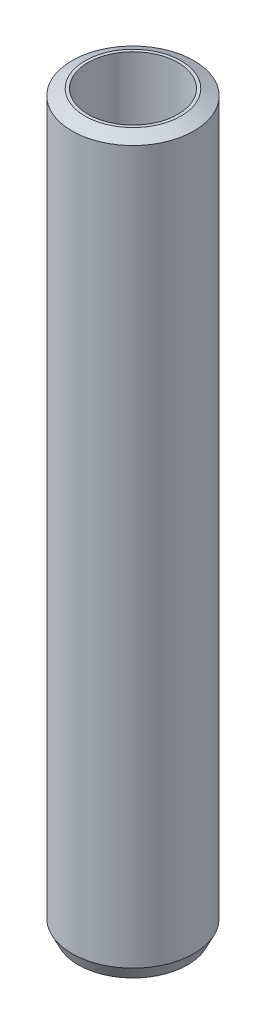
SolidWorks part; units mm, degrees
ref_plane "Front Plane" through (0, 0, 0) normal (0, 0, 1) x (1, 0, 0)
ref_plane "Top Plane" through (0, 0, 0) normal (0, 1, 0) x (1, 0, 0)
ref_plane "Right Plane" through (0, 0, 0) normal (1, 0, 0) x (0, 0, -1)
sketch "Sketch1" plane through (0, 0, 0) normal (0, 1, 0) x (1, 0, 0)
  circle A0 centre (0, 0) radius 50
  dimension "SHAFT_OD" = 100
extrude "Boss-Extrude1" add sketch "Sketch1" along normal blind 600
sketch "Sketch2" plane through (0, 0, 0) normal (0, 1, 0) x (1, 0, 0)
  circle A0 centre (0, 0) radius 36.8509
  dimension "BORE_D" = 73.7018
extrude "Cut-Extrude1" cut sketch "Sketch2" along normal through all
chamfer "Chamfer1" distance 5.2314 angle 63.895 2 edges at (0, 600, 50) (0, 0, 50) first distance on face at (0, 600, 50) first distance on face at (0, 0, 36.8509)
